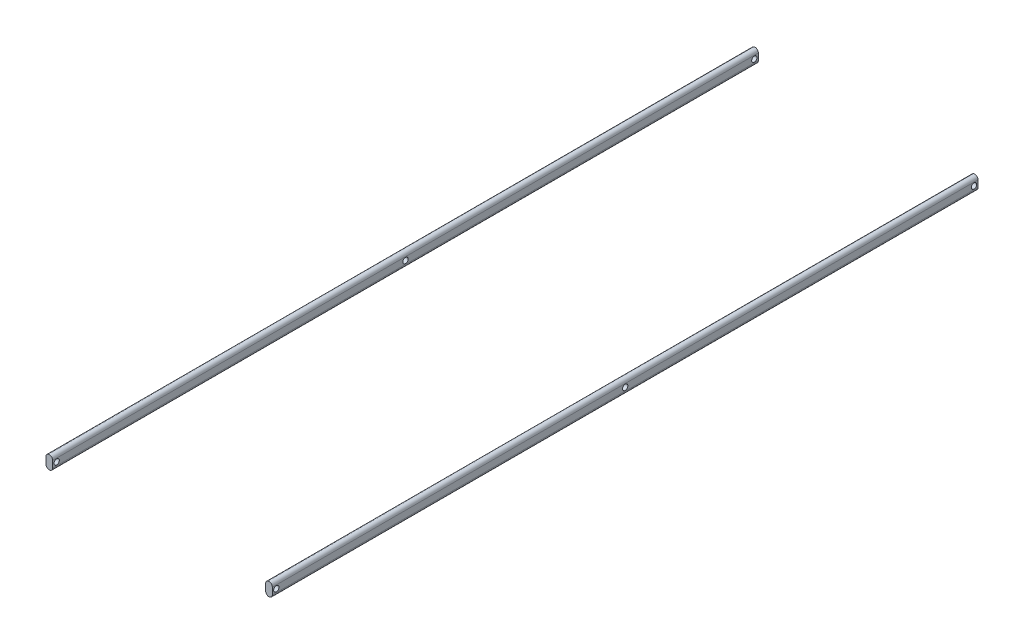
SolidWorks part; units mm, degrees
material "Cast Alloy Steel"
ref_plane "Front Plane" through (0, 0, 0) normal (0, 0, 1) x (1, 0, 0)
ref_plane "Top Plane" through (0, 0, 0) normal (0, 1, 0) x (1, 0, 0)
ref_plane "Right Plane" through (0, 0, 0) normal (1, 0, 0) x (0, 0, -1)
sketch "Sketch1" plane through (0, 0, 0) normal (0, 0, 1) x (1, 0, 0)
  line L0 (-75.2459, 15.2049) -> (-75.2459, 5.2049)
  line L1 (-75.2459, 5.2049) -> (94.7541, 5.2049)
  line L2 (94.7541, 5.2049) -> (94.7541, 15.2049)
  line L3 (94.7541, 15.2049) -> (89.7541, 15.2049)
  line L4 (89.7541, 15.2049) -> (89.7541, 10.2049)
  line L5 (89.7541, 10.2049) -> (-70.2459, 10.2049)
  line L6 (-70.2459, 10.2049) -> (-70.2459, 15.2049)
  line L7 (-70.2459, 15.2049) -> (-75.2459, 15.2049)
  dimension "D1" = 170
  dimension "D2" = 5
  dimension "D3" = 5
  dimension "D4" = 5
  dimension "D5" = 5
  dimension "D6" = 5
extrude "Boss-Extrude1" add sketch "Sketch1" along normal blind 100
sketch "Sketch2" plane through (0, 0, 100) normal (0, 0, 1) x (1, 0, 0)
  line L0 (-70.2459, 15.2049) -> (-75.2459, 15.2049) construction
  line L1 (94.7541, 5.2049) -> (94.7541, 15.2049) construction
  line L2 (94.7541, 15.2049) -> (89.7541, 15.2049) construction
  line L3 (89.7541, 15.2049) -> (89.7541, 10.2049) construction
  line L4 (-70.2459, 10.2049) -> (-70.2459, 15.2049) construction
  line L5 (-75.2459, 15.2049) -> (-75.2459, 5.2049) construction
  line L6 (-75.2459, 15.2049) -> (-75.2459, 5.2049)
  line L7 (-70.2459, 15.2049) -> (-75.2459, 15.2049)
  line L8 (-70.2459, 10.2049) -> (-70.2459, 15.2049)
  line L9 (89.7541, 15.2049) -> (89.7541, 10.2049)
  line L10 (94.7541, 15.2049) -> (89.7541, 15.2049)
  line L11 (94.7541, 5.2049) -> (94.7541, 15.2049)
  line L12 (-70.2459, 10.2049) -> (-70.2459, 5.2049)
  line L13 (-75.2459, 5.2049) -> (94.7541, 5.2049) construction
  line L14 (-70.2459, 5.2049) -> (-75.2459, 5.2049)
  line L15 (89.7541, 10.2049) -> (89.7541, 5.2049)
  line L16 (89.7541, 5.2049) -> (94.7541, 5.2049)
extrude "Boss-Extrude2" add sketch "Sketch2" along normal blind 430
sketch "Sketch3" plane through (94.7541, 0, 0) normal (1, 0, 0) x (0, 0, -1)
  line L0 (-530, 5.2049) -> (0, 5.2049) construction
  line L1 (0, 5.2049) -> (0, 15.2049) construction
  line L2 (-530, 5.2049) -> (-530, 15.2049) construction
  line L4 (-530, 5.2049) -> (0, 5.2049) construction
  point P0 (-3, 10.2049)
  point P3 (-527, 10.2049)
  point P6 (-265, 10.2049)
  dimension "D1" = 5
  dimension "D2" = 3
  dimension "D3" = 3
  dimension "D4" = 265
  dimension "D5" = 5
  dimension "D6" = 5
hole_wizard "Ø4.0mm Dowel Hole7" positions "Sketch4" profile "Sketch5" hole size "Ø4.0" standard "ANSI Metric" end condition through all
sketch "Sketch4" plane through (94.7541, 0, 0) normal (1, 0, 0) x (0, 0, -1)
  point P0 (-527, 10.2049)
  point P3 (-265, 10.2049)
  point P6 (-3, 10.2049)
sketch "Sketch5" plane through (94.7541, 10.2049, 527) normal (0, 1, 0) x (0, 0, -1)
  line L0 (0, 0) -> (0, 170)
  line L1 (0, 170) -> (2, 170)
  line L2 (2, 170) -> (2, 0)
  line L5 (2, 0) -> (0, 0)
  line L11 (0, -6.35) -> (0, 107.95) construction
  dimension "Thru Hole Dia." = 4
  dimension "Thru Hole Depth" = 170
sketch "Sketch6" plane through (0, 10.2049, 0) normal (0, 1, 0) x (1, 0, 0)
  line L1 (89.7541, 0) -> (-70.2459, 0)
  line L2 (89.7541, 0) -> (89.7541, -100)
  line L3 (89.7541, -100) -> (-70.2459, -100)
  line L4 (-70.2459, 0) -> (-70.2459, -100)
extrude "Cut-Extrude1" cut sketch "Sketch6" against normal blind 10
fillet "Fillet1" 2 edges at (94.7541, 15.2049, 265) (89.7541, 15.2049, 265) type full round first side face at (94.7541, 10.2049, 525) second side face at (89.7541, 10.2049, 265) middle face at (92.2541, 15.2049, 265)
fillet "Fillet2" 2 edges at (94.7541, 5.2049, 265) (89.7541, 5.2049, 265) type full round first side face at (94.7541, 10.2049, 525) second side face at (89.7541, 8.9549, 265) middle face at (92.2541, 5.2049, 265)
fillet "Fillet4" 2 edges at (-75.2459, 15.2049, 265) (-70.2459, 15.2049, 265) type full round first side face at (-75.2459, 10.2049, 525) second side face at (-70.2459, 10.2049, 265) middle face at (-72.7459, 15.2049, 265)
fillet "Fillet5" 2 edges at (-70.2459, 5.2049, 265) (-75.2459, 5.2049, 265) type full round first side face at (-70.2459, 8.9549, 265) second side face at (-75.2459, 10.2049, 525) middle face at (-72.7459, 5.2049, 265)
